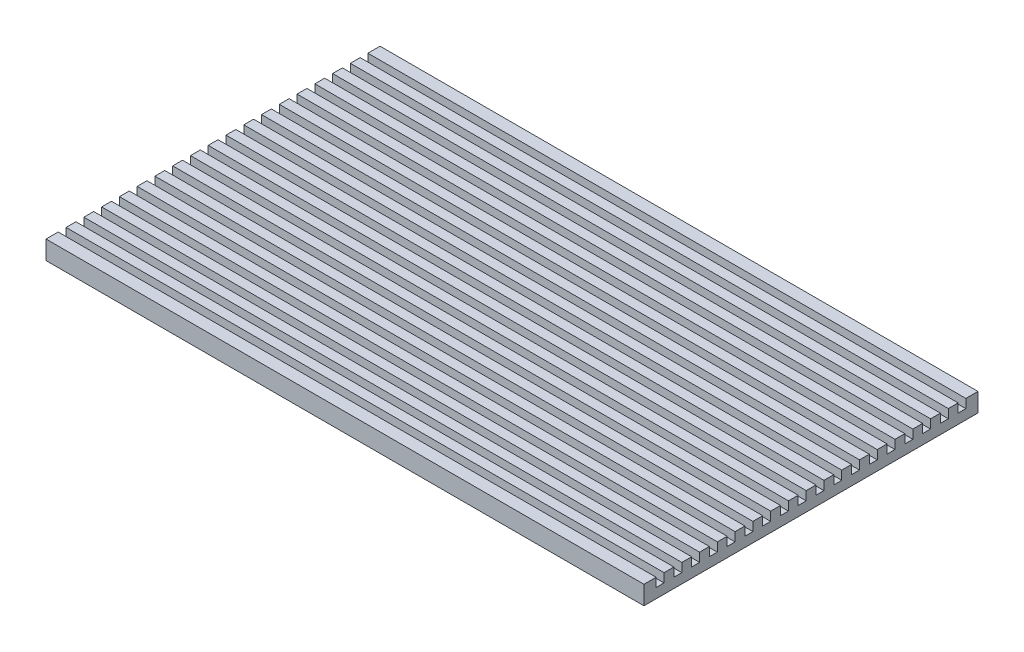
SolidWorks part; units mm, degrees
material "1060 Alloy"
ref_plane "Front Plane" through (0, 0, 0) normal (0, 0, 1) x (1, 0, 0)
ref_plane "Top Plane" through (0, 0, 0) normal (0, 1, 0) x (1, 0, 0)
ref_plane "Right Plane" through (0, 0, 0) normal (1, 0, 0) x (0, 0, -1)
sketch "Sketch1" plane through (0, 0, 0) normal (0, 1, 0) x (1, 0, 0)
  line L1 (64, 35.75) -> (-64, 35.75)
  line L2 (64, 35.75) -> (64, -35.75)
  line L3 (64, -35.75) -> (-64, -35.75)
  line L4 (-64, 35.75) -> (-64, -35.75)
  line L5 (64, 35.75) -> (-64, -35.75) construction
  line L6 (64, -35.75) -> (-64, 35.75) construction
  point P0 (0, 0)
  dimension "D1" = 71.5
  dimension "D2" = 128
extrude "Boss-Extrude1" add sketch "Sketch1" along normal blind 2.1 and the other way blind 0.0001
sketch "Sketch2" plane through (0, 2.1, 0) normal (0, 1, 0) x (1, 0, 0)
  line L0 (64, -35.75) -> (64, 35.75) construction
  line L1 (-64, -35.75) -> (64, -35.75)
  line L2 (-64, -35.75) -> (-64, -33.15)
  line L3 (-64, -33.15) -> (64, -33.15)
  line L4 (64, -35.75) -> (64, -33.15)
  line L6 (-64, 35.75) -> (64, 35.75)
  line L7 (-64, 35.75) -> (-64, 33.15)
  line L8 (-64, 33.15) -> (64, 33.15)
  line L9 (64, 35.75) -> (64, 33.15)
  dimension "D1" = 2.6
extrude "Boss-Extrude2" add sketch "Sketch2" along normal offset from surface (1.8999 mm away) 4 up to face at (0, -0.0001, 0)
sketch "Sketch3" plane through (0, 2.1, 0) normal (0, 1, 0) x (1, 0, 0)
  line L0 (-64, 33.15) -> (-64, -33.15) construction
  line L1 (-64, -31.45) -> (64, -31.45)
  line L2 (-64, -31.45) -> (-64, -29.35)
  line L3 (-64, -29.35) -> (64, -29.35)
  line L4 (64, -31.45) -> (64, -29.35)
  line L5 (64, -33.15) -> (64, 33.15) construction
  line L6 (-64, -33.15) -> (64, -33.15) construction
  dimension "D1" = 2.1
  dimension "D2" = 1.7
extrude "Boss-Extrude3" add sketch "Sketch3" along normal up to surface (1.8999 mm away) up to face at (0, 3.9999, 34.45)
pattern_linear "LPattern1" count 17 spacing 3.8031 along (0, 0, -1) of "Boss-Extrude3"
sketch "Sketch4" plane through (0, -0.0001, 0) normal (0, -1, 0) x (1, 0, 0)
  line L0 (64, -35.75) -> (-64, -35.75) construction
  line L1 (-64, -35.75) -> (-64, 35.75) construction
  line L2 (0, 0) -> (0, -35.75) construction
  line L5 (-64, 35.75) -> (64, 35.75) construction
  circle A0 centre (-51.4, -31.8) radius 1.2 construction
  circle A1 centre (0, -31.8) radius 1.2 construction
  circle A2 centre (51.4, -31.8) radius 1.2 construction
  circle A3 centre (-51.4, 5.5) radius 1.2 construction
  circle A4 centre (0, 5.5) radius 1.2 construction
  circle A5 centre (51.4, 5.5) radius 1.2 construction
  dimension "D1" = 2.4
  dimension "D3" = 11.4
  dimension "D4" = 49
  dimension "D5" = 34.9
  dimension "D6" = 29.05
  dimension "D2" = 2.75
sketch "Sketch5" plane through (0, -0.0001, 0) normal (0, -1, 0) x (1, 0, 0)
  circle A0 centre (-51.4, -31.8) radius 1.6 construction
  circle A1 centre (0, -31.8) radius 1.6 construction
  circle A2 centre (51.4, -31.8) radius 1.6 construction
  circle A3 centre (51.4, 5.5) radius 1.6 construction
  circle A4 centre (0, 5.5) radius 1.6 construction
  circle A5 centre (-51.4, 5.5) radius 1.6 construction
  dimension "D1" = 3.2
  dimension "D2" = 48.2
  dimension "D3" = 34.1
sketch "Sketch6" plane through (0, -0.0001, 0) normal (0, -1, 0) x (1, 0, 0)
  line L0 (0, 5.5) -> (0, -31.8) construction
  line L2 (-52.5, -22.775) -> (52.5, -22.775)
  line L3 (-52.5, -22.775) -> (-52.5, -3.525)
  line L4 (-52.5, -3.525) -> (52.5, -3.525)
  line L5 (52.5, -22.775) -> (52.5, -3.525)
  line L6 (-52.5, -22.775) -> (52.5, -3.525) construction
  line L7 (-52.5, -3.525) -> (52.5, -22.775) construction
  point P4 (0, -13.15)
  dimension "D1" = 19.25
  dimension "D2" = 105
extrude "Boss-Extrude4" add sketch "Sketch6" along normal blind 5.5
